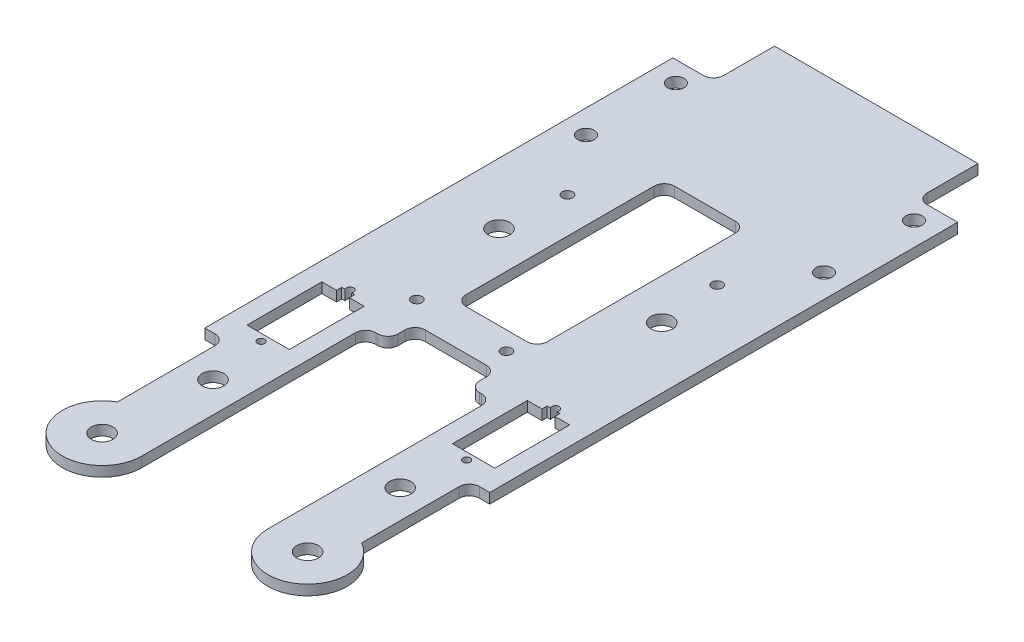
SolidWorks part; units mm, degrees
material "6061-T4 (SS)"
ref_plane "Front Plane" through (0, 0, 0) normal (0, 0, 1) x (1, 0, 0)
ref_plane "Top Plane" through (0, 0, 0) normal (0, 1, 0) x (1, 0, 0)
ref_plane "Right Plane" through (0, 0, 0) normal (1, 0, 0) x (0, 0, -1)
sketch "Sketch1" plane through (0, 0, 0) normal (0, 1, 0) x (1, 0, 0)
  line L1 (-44.45, -114.3) -> (44.45, -114.3)
  line L2 (-44.45, -114.3) -> (-44.45, 114.3)
  line L3 (-44.45, 114.3) -> (44.45, 114.3)
  line L4 (44.45, -114.3) -> (44.45, 114.3)
  line L5 (-44.45, -114.3) -> (44.45, 114.3) construction
  line L6 (-44.45, 114.3) -> (44.45, -114.3) construction
  point P0 (0, 0)
  dimension "D1" = 88.9
  dimension "D2" = 228.6
extrude "Boss-Extrude1" add sketch "Sketch1" along normal blind 3.175
sketch "Sketch11" plane through (0, 3.175, 0) normal (0, 1, 0) x (1, 0, 0)
  line L0 (0, 31.75) -> (97.4414, 31.75) construction
  line L10 (0, 0) -> (0, 114.3) construction
  line L14 (44.45, 114.3) -> (-44.45, 114.3) construction
  line L15 (0, 0) -> (117.475, 0) construction
  circle A0 centre (-26.289, 4.9828) radius 1.25
  circle A1 centre (-25.019, 53.1832) radius 1.25
  circle A2 centre (25.781, 38.1972) radius 1.25
  circle A3 centre (25.781, 10.0628) radius 1.25
  dimension "D3" = 2.5
  dimension "D5" = 2.5
  dimension "D7" = 31.75
  dimension "D9" = 25.781
  dimension "D4" = 2.5
  dimension "D6" = 2.5
  dimension "D2" = 25.019
  dimension "D8" = 26.289
  dimension "D10" = 6.4472
  dimension "D11" = 25.781
  dimension "D12" = 21.6872
  dimension "D13" = 26.7672
  dimension "D14" = 21.4332
extrude "Cut-Extrude12" [suppressed] cut sketch "Sketch11" against normal through all
sketch "Sketch18" plane through (0, 3.175, 0) normal (0, 1, 0) x (1, 0, 0)
  line L0 (44.45, 79.883) -> (-44.45, 79.883) construction
  line L1 (44.45, -114.3) -> (44.45, 114.3) construction
  line L2 (-44.45, 114.3) -> (-44.45, -114.3) construction
  line L3 (44.45, 114.3) -> (-44.45, 114.3) construction
  line L4 (0, 79.883) -> (0, -114.3) construction
  line L5 (-44.45, -114.3) -> (44.45, -114.3) construction
  line L6 (19.05, 79.883) -> (19.05, 6.35) construction
  line L7 (-19.05, 79.883) -> (-19.05, 6.35) construction
  line L8 (19.05, 6.35) -> (-19.05, 6.35) construction
  circle A0 centre (-23.876, 60.833) radius 1.6319
  circle A1 centre (23.876, 59.817) radius 1.6319
  circle A2 centre (-19.05, 9.017) radius 1.632
  circle A3 centre (8.89, 9.017) radius 1.632
  dimension "D4" = 3.2639
  dimension "D9" = 3.2639
  dimension "D11" = 3.2639
  dimension "D13" = 3.2639
  dimension "D1" = 34.417
  dimension "D2" = 19.05
  dimension "D3" = 73.533
  dimension "D5" = 23.876
  dimension "D6" = 19.05
  dimension "D7" = 23.876
  dimension "D8" = 1.016
  dimension "D10" = 4.826
  dimension "D12" = 51.816
  dimension "D14" = 0
  dimension "D15" = 27.94
sketch "Sketch12" plane through (0, 3.175, 0) normal (0, 1, 0) x (1, 0, 0)
  line L0 (0, 0) -> (44.45, 0) construction
  line L1 (44.45, -114.3) -> (44.45, 114.3) construction
  line L2 (0, 0) -> (0, 114.3) construction
  line L3 (44.45, 114.3) -> (-44.45, 114.3) construction
  line L4 (44.45, -44.45) -> (-44.45, -44.45) construction
  line L5 (-19.685, -69.85) -> (19.685, -69.85)
  line L6 (-19.685, -69.85) -> (-19.685, -6.35)
  line L7 (-19.685, -6.35) -> (19.685, -6.35)
  line L8 (19.685, -69.85) -> (19.685, -6.35)
  line L9 (-19.685, -69.85) -> (19.685, -6.35) construction
  line L10 (-19.685, -6.35) -> (19.685, -69.85) construction
  line L11 (-44.45, 114.3) -> (-44.45, -114.3) construction
  line L12 (0, -38.1) -> (0, -114.3) construction
  line L13 (-44.45, -114.3) -> (44.45, -114.3) construction
  circle A0 centre (29.21, -44.45) radius 3.3782
  circle A1 centre (-29.21, -44.45) radius 3.3782
  point P5 (0, -38.1)
  dimension "D5" = 6.7564
  dimension "D1" = 63.5
  dimension "D2" = 38.1
  dimension "D3" = 39.37
  dimension "D4" = 25.4
  dimension "D6" = 58.42
extrude "Cut-Extrude13" cut sketch "Sketch12" against normal through all
sketch "Sketch14" plane through (0, 0, 0) normal (0, -1, 0) x (-1, 0, 0)
  line L0 (0, 114.3) -> (0, 31.056) construction
  line L1 (-44.45, 114.3) -> (44.45, 114.3) construction
  line L2 (0, 114.3) -> (-44.45, 114.3) construction
  line L3 (-41.91, 114.3) -> (-41.91, 67.4804) construction
  line L5 (-32.385, 114.3) -> (-32.385, 67.4804) construction
  line L6 (-32.385, 107.95) -> (-41.91, 107.95) construction
  line L7 (-32.385, 93.9165) -> (-41.91, 93.9165) construction
  line L8 (-44.45, -114.3) -> (-44.45, 114.3) construction
  circle A0 centre (-37.1475, 107.95) radius 2.5527
  circle A1 centre (-37.1475, 79.883) radius 2.5527
  circle A2 centre (37.1475, 107.95) radius 2.5527
  circle A3 centre (37.1475, 79.883) radius 2.5527
  dimension "D4" = 5.1054
  dimension "D1" = 2.54
  dimension "D2" = 9.525
  dimension "D3" = 6.35
  dimension "D5" = 14.0335
extrude "Cut-Extrude15" cut sketch "Sketch14" against normal through all
sketch "Sketch15" plane through (0, 0, 0) normal (0, -1, 0) x (1, 0, 0)
  line L0 (44.45, 114.3) -> (44.45, -114.3) construction
  line L1 (-44.45, 114.3) -> (44.45, 114.3)
  line L2 (-44.45, 114.3) -> (-44.45, 57.15)
  line L3 (-44.45, 57.15) -> (44.45, 57.15)
  line L4 (44.45, 114.3) -> (44.45, 57.15)
  line L5 (19.685, 6.35) -> (-19.685, 6.35) construction
  line L6 (0, -36.7665) -> (0, -114.3) construction
  line L7 (12.7, -76.708) -> (12.7, -17.9917)
  line L8 (9.525, -14.8167) -> (-9.525, -14.8167)
  line L9 (44.45, -114.3) -> (-44.45, -114.3) construction
  line L10 (-12.7, -17.9917) -> (-12.7, -76.708)
  line L11 (9.525, -79.883) -> (-9.525, -79.883)
  line L12 (12.7, -76.708) -> (12.7, 6.35) construction
  line L13 (12.7, 6.35) -> (-12.7, 6.35) construction
  line L14 (-12.7, -76.708) -> (-12.7, 6.35) construction
  line L15 (12.7, -79.883) -> (-12.7, 6.35) construction
  line L16 (12.7, 6.35) -> (-12.7, -79.883) construction
  line L17 (12.7, 6.35) -> (-12.7, 6.35)
  line L18 (-12.7, 6.35) -> (-12.7, 1.0583)
  line L19 (-9.525, -2.1167) -> (9.525, -2.1167)
  line L20 (12.7, 1.0583) -> (12.7, 6.35)
  circle A0 centre (-29.21, 44.45) radius 3.3782 construction
  circle A1 centre (-37.1475, -79.883) radius 2.5527 construction
  arc A2 (-9.525, -79.883) -> (-12.7, -76.708) centre (-9.525, -76.708) cw
  arc A3 (9.525, -79.883) -> (12.7, -76.708) centre (9.525, -76.708) ccw
  arc A4 (12.7, -17.9917) -> (9.525, -14.8167) centre (9.525, -17.9917) ccw
  arc A5 (-9.525, -14.8167) -> (-12.7, -17.9917) centre (-9.525, -17.9917) ccw
  arc A6 (-12.7, 1.0583) -> (-9.525, -2.1167) centre (-9.525, 1.0583) ccw
  arc A7 (9.525, -2.1167) -> (12.7, 1.0583) centre (9.525, 1.0583) ccw
  point P35 (12.7, -14.8167)
  point P38 (-12.7, -14.8167)
  point P41 (-12.7, -2.1167)
  point P44 (12.7, -2.1167)
  dimension "D3" = 3.175
  dimension "D7" = 3.175
  dimension "D1" = 12.7
  dimension "D2" = 0
  dimension "D4" = 25.4
  dimension "D5" = 8.4667
  dimension "D6" = 12.7
extrude "Cut-Extrude16" cut sketch "Sketch15" against normal through all
fillet "Fillet1" radius 3.175 4 edges at (19.685, 1.5875, 6.35) (-19.685, 1.5875, 6.35) (-12.7, 1.5875, 6.35) (12.7, 1.5875, 6.35)
extrude "Cut-Extrude18" cut sketch "Sketch18" against normal through all
sketch "Sketch16" plane through (0, 3.175, 0) normal (0, 1, 0) x (1, 0, 0)
  line L0 (44.45, -57.15) -> (44.45, -76.2)
  line L1 (19.685, -57.15) -> (19.685, -76.2)
  line L2 (19.685, -76.2) -> (44.45, -76.2) construction
  line L3 (0, 0) -> (0, -94.827) construction
  line L4 (44.45, -57.15) -> (19.685, -57.15)
  line L5 (-19.685, -57.15) -> (-19.685, -76.2)
  line L6 (-44.45, -57.15) -> (-19.685, -57.15)
  line L7 (-44.45, -57.15) -> (-44.45, -76.2)
  arc A0 (44.45, -76.2) -> (19.685, -76.2) centre (32.0675, -76.2) cw
  arc A1 (-44.45, -76.2) -> (-19.685, -76.2) centre (-32.0675, -76.2) ccw
  circle A2 centre (32.0675, -76.2) radius 3.3782
  circle A3 centre (-32.0675, -76.2) radius 3.3782
  line M12 (-44.45, -57.15) -> (-19.685, -57.15)
  line M16 (19.685, -57.15) -> (44.45, -57.15)
  dimension "D2" = 6.7564
  dimension "D1" = 19.05
extrude "Boss-Extrude2" add sketch "Sketch16" against normal up to surface (3.175 mm away) contours L7 A1 L5 A3 M12 | A0 L0 L1 A2 M16 region at (32.0675, 3.175, 71.4304) region at (-32.0675, 3.175, 71.4304) up to face at (-23.876, 0, -59.2011)
sketch "Sketch17" plane through (0, 3.175, 0) normal (0, 1, 0) x (1, 0, 0)
  line L0 (38.1, -65.3863) -> (38.1, -34.925)
  line L1 (44.45, -76.2) -> (44.45, 114.3) construction
  line L9 (0, 0) -> (0, -71.3802) construction
  line L15 (41.275, -31.75) -> (44.45, -31.75)
  line L20 (44.45, -31.75) -> (44.45, -76.2)
  line L21 (-41.275, -31.75) -> (-44.45, -31.75)
  line L22 (-38.1, -65.3863) -> (-38.1, -34.925)
  line L23 (-44.45, -31.75) -> (-44.45, -76.2)
  circle A4 centre (32.0675, -76.2) radius 3.3046 construction
  arc A5 (38.1, -34.925) -> (41.275, -31.75) centre (41.275, -34.925) cw
  circle A10 centre (32.0675, -76.2) radius 12.3825 construction
  arc A11 (38.1, -65.3863) -> (44.45, -76.2) centre (32.0675, -76.2) cw
  arc A12 (-38.1, -34.925) -> (-41.275, -31.75) centre (-41.275, -34.925) ccw
  arc A13 (-38.1, -65.3863) -> (-44.45, -76.2) centre (-32.0675, -76.2) ccw
  point P11 (38.1, -31.75)
  dimension "D2" = 3.175
  dimension "D3" = 44.45
  dimension "D1" = 6.35
extrude "Cut-Extrude17" cut sketch "Sketch17" against normal through all
sketch "Sketch19" plane through (0, 3.175, 0) normal (0, 1, 0) x (1, 0, 0)
  line L0 (0, 14.8167) -> (0, 79.883) construction
  line L1 (9.525, 14.8167) -> (-9.525, 14.8167) construction
  line L2 (-9.525, 79.883) -> (9.525, 79.883) construction
  line L3 (-12.7, 47.3498) -> (12.7, 47.3498) construction
  line L4 (-12.7, 17.9917) -> (-12.7, 76.708) construction
  line L5 (12.7, 76.708) -> (12.7, 17.9917) construction
  line L6 (-38.1, 53.975) -> (-12.7, 53.975) construction
  line L7 (-25.4, 53.975) -> (-25.4, 40.9998) construction
  line L9 (-44.45, 114.3) -> (-44.45, -31.75) construction
  circle A0 centre (-25.4, 40.9998) radius 3.3782
  circle A1 centre (25.4, 40.9998) radius 3.3782
  dimension "D1" = 6.7564
  dimension "D2" = 6.35
  dimension "D3" = 6.35
extrude "Cut-Extrude19" cut sketch "Sketch19" against normal through all
sketch "Sketch20" plane through (0, 3.175, 0) normal (0, 1, 0) x (1, 0, 0)
  line L0 (0, 0) -> (0, 61.1006) construction
  line L3 (-25.8445, 3.175) -> (-25.8445, -28.575) construction
  line L6 (-25.4635, -1.016) -> (-38.6715, -1.016) construction
  line L7 (-25.4635, -1.016) -> (-25.4635, -24.384)
  line L8 (-25.4635, -24.384) -> (-38.6715, -24.384)
  line L9 (-38.6715, -1.016) -> (-38.6715, -24.384)
  line L10 (-25.4635, -1.016) -> (-38.6715, -24.384) construction
  line L11 (-25.4635, -24.384) -> (-38.6715, -1.016) construction
  line L13 (-38.2905, 3.175) -> (-38.2905, -28.575) construction
  line L14 (-25.8445, 3.175) -> (-38.2905, -28.575) construction
  line L27 (-32.0675, -76.2) -> (-32.0675, 23.1424) construction
  line L28 (-38.2905, 3.175) -> (-25.8445, -28.575) construction
  line L29 (-38.2905, -28.575) -> (-32.9565, -28.575) construction
  line L30 (-32.9565, -28.575) -> (-32.9565, -27.305) construction
  line L31 (-31.1785, -28.575) -> (-31.1785, -27.305) construction
  line L32 (-25.8445, -28.575) -> (-31.1785, -28.575) construction
  line L33 (-25.8445, 3.175) -> (-31.1785, 3.175) construction
  line L34 (-31.1785, 3.175) -> (-31.1785, 1.905) construction
  line L35 (-32.9565, 3.175) -> (-32.9565, 1.905) construction
  line L36 (-38.2905, 3.175) -> (-32.9565, 3.175) construction
  line L38 (-30.0355, -1.016) -> (-30.0355, 0.6151)
  line L42 (-30.0355, -1.016) -> (-25.4635, -1.016)
  line L44 (-34.0995, -1.016) -> (-34.0995, 0.6151)
  line L45 (-34.0995, -1.016) -> (-38.6715, -1.016)
  line L47 (-33.0574, 0.6151) -> (-34.0995, 0.6151)
  line L48 (-32.0675, 1.1866) -> (-32.0675, 0.0436) construction
  line L49 (-32.0675, 1.1866) -> (-32.0675, 0.0436) construction
  line L50 (-32.0675, 0.6151) -> (-30.8266, 0.6151) construction
  line L51 (-30.0355, 0.6151) -> (-31.0776, 0.6151)
  line L52 (30.0355, -1.016) -> (30.0355, 0.6151)
  line L53 (30.0355, -1.016) -> (25.4635, -1.016)
  line L54 (25.4635, -1.016) -> (25.4635, -24.384)
  line L55 (25.4635, -24.384) -> (38.6715, -24.384)
  line L56 (38.6715, -1.016) -> (38.6715, -24.384)
  line L57 (34.0995, -1.016) -> (38.6715, -1.016)
  line L58 (34.0995, -1.016) -> (34.0995, 0.6151)
  line L59 (33.0574, 0.6151) -> (34.0995, 0.6151)
  line L60 (30.0355, 0.6151) -> (31.0776, 0.6151)
  arc A0 (-32.9565, -27.305) -> (-31.1785, -27.305) centre (-32.0675, -26.5866) cw construction
  arc A1 (-32.9565, 1.905) -> (-31.1785, 1.905) centre (-32.0675, 1.1866) ccw construction
  circle A2 centre (-32.0675, 1.1866) radius 1.143 construction
  circle A3 centre (-32.0675, -26.5866) radius 1.143
  circle A4 centre (32.0675, -26.5866) radius 1.143
  arc A7 (-33.0574, 0.6151) -> (-31.0776, 0.6151) centre (-32.0675, 1.1866) cw
  arc A8 (33.0574, 0.6151) -> (31.0776, 0.6151) centre (32.0675, 1.1866) ccw
  point P10 (-32.0675, -12.7)
  point P16 (-32.0675, -12.7)
  dimension "D1" = 13.208
  dimension "D2" = 23.368
  dimension "D3" = 63.5
  dimension "D4" = 2.032
extrude "Cut-Extrude20" cut sketch "Sketch20" against normal through all
sketch "Sketch21" plane through (0, 0, -114.3) normal (0, 0, -1) x (-1, 0, 0)
  line L1 (44.45, 0) -> (-44.45, 0)
  line L2 (44.45, 0) -> (44.45, 3.175)
  line L3 (44.45, 3.175) -> (-44.45, 3.175)
  line L4 (-44.45, 0) -> (-44.45, 3.175)
extrude "Boss-Extrude3" add sketch "Sketch21" along normal blind 19.05
sketch "Sketch22" plane through (0, 3.175, 0) normal (0, 1, 0) x (1, 0, 0)
  line L0 (0, 79.883) -> (0, 133.35) construction
  line L1 (-44.45, 133.35) -> (-31.75, 133.35)
  line L2 (-44.45, 133.35) -> (-44.45, 114.3)
  line L3 (-44.45, 114.3) -> (-34.925, 114.3)
  line L4 (-31.75, 133.35) -> (-31.75, 117.475)
  line L5 (-9.525, 79.883) -> (9.525, 79.883) construction
  line L6 (44.45, 133.35) -> (-44.45, 133.35) construction
  line L7 (44.45, 114.3) -> (34.925, 114.3)
  line L8 (31.75, 133.35) -> (31.75, 117.475)
  line L9 (44.45, 133.35) -> (31.75, 133.35)
  line L10 (44.45, 133.35) -> (44.45, 114.3)
  arc A0 (-34.925, 114.3) -> (-31.75, 117.475) centre (-34.925, 117.475) ccw
  arc A1 (34.925, 114.3) -> (31.75, 117.475) centre (34.925, 117.475) cw
  point P13 (-31.75, 114.3)
  dimension "D3" = 3.175
  dimension "D1" = 12.7
  dimension "D2" = 19.05
extrude "Cut-Extrude21" cut sketch "Sketch22" against normal through all
